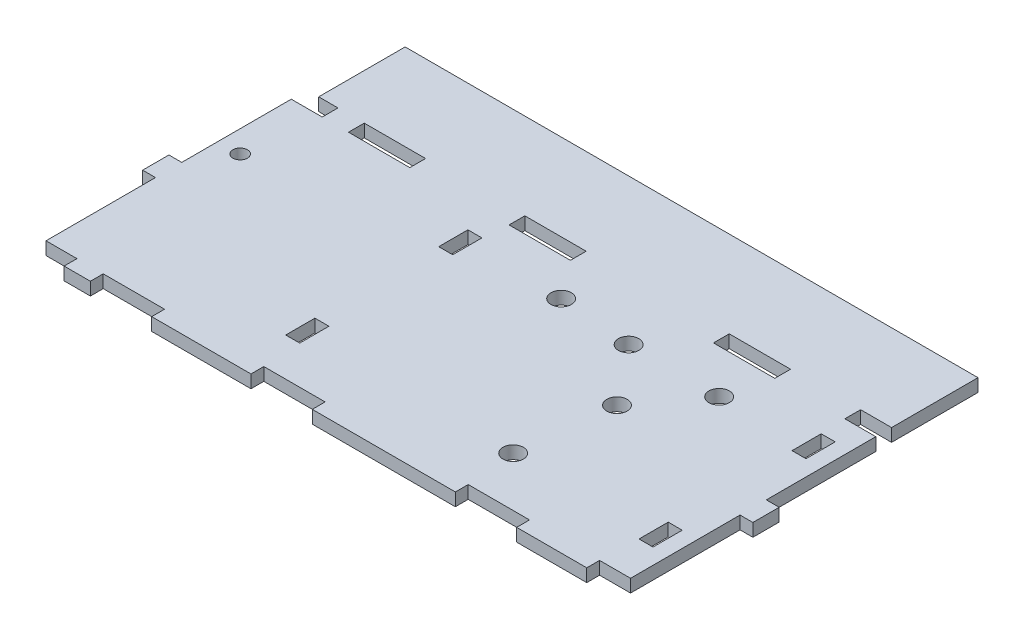
SolidWorks part; units mm, degrees
ref_plane "Front Plane" through (0, 0, 0) normal (0, 0, 1) x (1, 0, 0)
ref_plane "Top Plane" through (0, 0, 0) normal (0, 1, 0) x (1, 0, 0)
ref_plane "Right Plane" through (0, 0, 0) normal (1, 0, 0) x (0, 0, -1)
sketch "Sketch1" plane through (0, 0, 0) normal (0, 1, 0) x (1, 0, 0)
  line L0 (-110.6901, 12.3801) -> (-116.2781, 12.3801)
  line L2 (-110.6901, -46.6749) -> (-110.6901, 0.9501)
  line L4 (143.5639, -46.6749) -> (143.5639, 0.9501)
  line L5 (-110.6901, -46.6749) -> (143.5639, 60.0051) construction
  line L6 (-110.6901, 60.0051) -> (143.5639, -46.6749) construction
  line L7 (-116.2781, 12.3801) -> (-116.2781, 0.9501)
  line L8 (-116.2781, 0.9501) -> (-110.6901, 0.9501)
  line L9 (-110.6901, 12.3801) -> (-110.6901, 60.0051)
  line L10 (10.7219, 63.4341) -> (72.9519, 63.4341) construction
  line L11 (149.1519, 0.9501) -> (143.5639, 0.9501)
  line L12 (149.1519, 12.3801) -> (149.1519, 0.9501)
  line L13 (143.5639, 12.3801) -> (149.1519, 12.3801)
  line L14 (143.5639, 12.3801) -> (143.5639, 60.0051)
  line L23 (-108.712, 0) -> (106.818, 0) construction
  line L32 (-110.6901, 60.0051) -> (-97.2281, 60.0051)
  line L33 (-110.6901, -46.6749) -> (-97.2281, -46.6749)
  line L34 (-85.7981, 60.0051) -> (-59.1281, 60.0051)
  line L36 (-97.2281, 60.0051) -> (-97.2281, 66.8631)
  line L38 (-85.7981, 60.0051) -> (-85.7981, 66.8631)
  line L40 (-59.1281, 60.0051) -> (-59.1281, 66.8631)
  line L42 (-15.9481, 60.0051) -> (-15.9481, 66.8631)
  line L44 (10.7219, 60.0051) -> (10.7219, 66.8631)
  line L46 (72.9519, 60.0051) -> (72.9519, 66.8631)
  line L48 (99.6219, 60.0051) -> (99.6219, 66.8631)
  line L50 (130.1019, 60.0051) -> (130.1019, 66.8631)
  line L51 (-15.9481, 60.0051) -> (10.7219, 60.0051)
  line L52 (72.9519, 60.0051) -> (99.6219, 60.0051)
  line L53 (130.1019, 60.0051) -> (143.5639, 60.0051)
  line L54 (130.1019, -46.6749) -> (130.1019, -52.2629)
  line L55 (99.6219, -52.2629) -> (130.1019, -52.2629)
  line L56 (99.6219, -46.6749) -> (99.6219, -52.2629)
  line L57 (72.9519, -46.6749) -> (72.9519, -52.2629)
  line L58 (10.7219, -52.2629) -> (72.9519, -52.2629)
  line L59 (10.7219, -46.6749) -> (10.7219, -52.2629)
  line L60 (-15.9481, -46.6749) -> (-15.9481, -52.2629)
  line L61 (-59.1281, -52.2629) -> (-15.9481, -52.2629)
  line L62 (-59.1281, -46.6749) -> (-59.1281, -52.2629)
  line L63 (-85.7981, -46.6749) -> (-85.7981, -52.2629)
  line L64 (-97.2281, -52.2629) -> (-85.7981, -52.2629)
  line L65 (-97.2281, -46.6749) -> (-97.2281, -52.2629)
  line L66 (-85.7981, -46.6749) -> (-59.1281, -46.6749)
  line L67 (-15.9481, -46.6749) -> (10.7219, -46.6749)
  line L68 (72.9519, -46.6749) -> (99.6219, -46.6749)
  line L69 (130.1019, -46.6749) -> (143.5639, -46.6749)
  line L70 (130.1019, 66.8631) -> (143.5639, 66.8631)
  line L71 (143.5639, 66.8631) -> (143.5639, 104.4551)
  line L72 (-97.2281, 66.8631) -> (-105.6101, 66.8631)
  line L73 (-105.6101, 66.8631) -> (-105.6101, 104.4551)
  line L74 (-105.6101, 104.4551) -> (143.5639, 104.4551)
  line L75 (99.6219, 66.8631) -> (72.9519, 66.8631)
  line L76 (10.7219, 66.8631) -> (-15.9481, 66.8631)
  line L77 (-59.1281, 66.8631) -> (-85.7981, 66.8631)
  line L78 (-97.2281, 63.4341) -> (-85.7981, 63.4341) construction
  line L79 (-91.5131, 63.4341) -> (-91.5131, -53.3153) construction
  line L80 (-59.1281, 63.4341) -> (-15.9481, 63.4341) construction
  line L81 (-37.5381, 63.4341) -> (-37.5381, -52.2629) construction
  line L82 (41.8369, 63.4341) -> (41.8369, -52.2629) construction
  line L83 (99.6219, 63.4341) -> (130.1019, 63.4341) construction
  line L84 (114.8619, 63.4341) -> (114.8619, -52.2629) construction
  point P0 (0, 0)
  point P57 (-91.5131, -52.2629)
  point P63 (-37.5381, -52.2629)
  point P66 (41.8369, -52.2629)
  dimension "D1" = 106.68
  dimension "D3" = 11.43
  dimension "D4" = 5.588
  dimension "D5" = 6.858
  dimension "D6" = 11.43
  dimension "D7" = 26.67
  dimension "D8" = 13.462
  dimension "D10" = 106.68
  dimension "D11" = 11.43
  dimension "D12" = 6.858
  dimension "D13" = 37.592
  dimension "D14" = 5.588
  dimension "D15" = 5.588
  dimension "D16" = 47.625
  dimension "D17" = 47.625
  dimension "D18" = 47.625
  dimension "D19" = 47.625
  dimension "D20" = 62.23
  dimension "D21" = 11.43
  dimension "D23" = 43.18
  dimension "D26" = 26.67
  dimension "D27" = 30.48
  dimension "D28" = 13.462
  dimension "D29" = 110.6901
  dimension "D30" = 26.67
  dimension "D31" = 43.18
  dimension "D32" = 62.23
  dimension "D33" = 26.67
  dimension "D34" = 30.48
  dimension "D35" = 8.382
extrude "Boss-Extrude1" add sketch "Sketch1" along normal blind 5.588
sketch "Sketch9" plane through (0, 5.588, 0) normal (0, 1, 0) x (1, 0, 0)
  line L0 (-110.6901, 0.9501) -> (-110.6901, -46.6749) construction
  line L1 (-23.0601, -17.3379) -> (-16.9641, -17.3379)
  line L2 (-23.0601, -17.3379) -> (-23.0601, -30.0379)
  line L3 (-23.0601, -30.0379) -> (-16.9641, -30.0379)
  line L4 (-16.9641, -17.3379) -> (-16.9641, -30.0379)
  line L5 (-85.7981, -46.6749) -> (-59.1281, -46.6749) construction
  line L6 (-23.0601, 36.5101) -> (-16.9641, 36.5101)
  line L7 (-23.0601, 36.5101) -> (-23.0601, 49.2101)
  line L8 (-23.0601, 49.2101) -> (-16.9641, 49.2101)
  line L9 (-16.9641, 36.5101) -> (-16.9641, 49.2101)
  line L10 (130.6099, -17.3379) -> (136.7059, -17.3379)
  line L11 (130.6099, -17.3379) -> (130.6099, -30.0379)
  line L12 (130.6099, -30.0379) -> (136.7059, -30.0379)
  line L13 (136.7059, -17.3379) -> (136.7059, -30.0379)
  line L14 (130.6099, 49.2101) -> (136.7059, 49.2101)
  line L15 (130.6099, 49.2101) -> (130.6099, 36.5101)
  line L16 (130.6099, 36.5101) -> (136.7059, 36.5101)
  line L17 (136.7059, 49.2101) -> (136.7059, 36.5101)
  line L18 (143.5639, -46.6749) -> (143.5639, 0.9501) construction
  line L19 (143.5639, 12.3801) -> (143.5639, 60.0051) construction
  dimension "D1" = 12.7
  dimension "D2" = 6.096
  dimension "D3" = 87.63
  dimension "D4" = 16.637
  dimension "D5" = 87.63
  dimension "D6" = 83.185
  dimension "D7" = 12.7
  dimension "D8" = 6.096
  dimension "D9" = 12.7
  dimension "D10" = 6.096
  dimension "D11" = 6.096
  dimension "D12" = 12.7
  dimension "D13" = 6.858
  dimension "D14" = 6.858
extrude "Cut-Extrude1" cut sketch "Sketch9" against normal up to next
sketch "Sketch12" plane through (0, 5.588, 0) normal (0, 1, 0) x (1, 0, 0)
  line L0 (-97.2281, 60.0051) -> (-110.6901, 60.0051) construction
  line L1 (-110.6901, 60.0051) -> (-110.6901, 12.3801) construction
  circle A0 centre (-101.1651, 28.2551) radius 3.175
  point P4 (-103.9591, 60.0051)
  dimension "D1" = 6.35
  dimension "D2" = 31.75
  dimension "D3" = 9.525
extrude "Cut-Extrude2" cut sketch "Sketch12" against normal up to next
sketch "Sketch13" plane through (0, 0, 0) normal (0, -1, 0) x (1, 0, 0)
  line L0 (72.9519, -60.0051) -> (99.6219, -60.0051) construction
  line L1 (73.9719, 25.8949) -> (73.9719, 36.1949) construction
  line L2 (22.3189, -40.5328) -> (12.0189, -40.5328) construction
  line L3 (6.6189, -18.8828) -> (6.6189, -39.6828) construction
  line L4 (73.1219, 41.5949) -> (52.3219, 41.5949) construction
  circle A0 centre (70.9239, 25.0849) radius 4.445
  circle A2 centre (55.0998, -40.9551) radius 4.445
  circle A3 centre (94.4744, -40.9551) radius 4.445
  circle A4 centre (75.4244, -15.5551) radius 4.445
  circle A5 centre (23.1289, -43.5808) radius 4.445
  point P14 (74.4393, 37.6318)
  point P15 (70.9915, 38.8651)
  point P16 (5.7689, -36.4104)
  point P17 (81.9689, 9.8449)
  point P18 (81.9689, 29.1678)
  point P19 (81.9689, 36.6944)
  point P20 (81.9689, 40.7683)
  point P21 (97.97, -40.9551)
  point P22 (0, 0)
  point P23 (0, 0)
  point P24 (23.6324, -43.125)
  point P25 (0, 0)
  point P26 (72.3658, -15.5551)
  point P27 (0, 0)
  point P28 (94.4744, -40.9551)
  point P29 (55.0998, -40.9551)
  point P30 (75.4506, -15.5551)
  point P31 (0, 0)
  point P34 (17.1689, -40.5328)
  dimension "D1" = 19.05
  dimension "D2" = 3.048
  dimension "D3" = 8.89
  dimension "D4" = 3.048
  dimension "D5" = 16.51
  dimension "D6" = 16.51
  dimension "D8" = 19.05
extrude "Cut-Extrude3" cut sketch "Sketch13" against normal up to next
sketch "Sketch14" plane through (0, 5.588, 0) normal (0, 1, 0) x (1, 0, 0)
  line L0 (143.5639, -46.6749) -> (143.5639, 0.9501) construction
  line L1 (137.2139, 0.9501) -> (140.3889, 0.9501)
  line L2 (137.2139, 0.9501) -> (137.2139, 13.6501)
  line L3 (137.2139, 13.6501) -> (140.3889, 13.6501)
  line L4 (140.3889, 0.9501) -> (140.3889, 13.6501)
  line L5 (143.5639, 0.9501) -> (149.1519, 0.9501) construction
  dimension "D1" = 3.175
  dimension "D2" = 12.7
  dimension "D3" = 3.175
